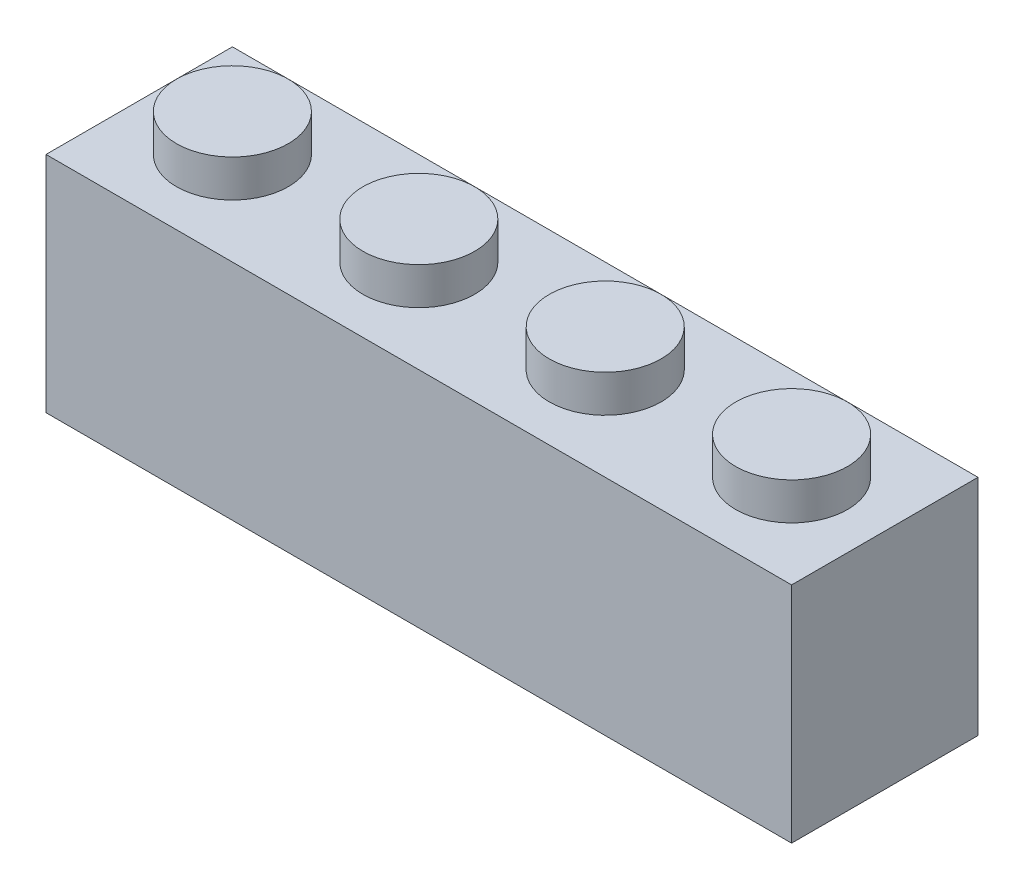
SolidWorks part; units mm, degrees
ref_plane "Front Plane" through (0, 0, 0) normal (0, 0, 1) x (1, 0, 0)
ref_plane "Top Plane" through (0, 0, 0) normal (0, 1, 0) x (1, 0, 0)
ref_plane "Right Plane" through (0, 0, 0) normal (1, 0, 0) x (0, 0, -1)
sketch "Sketch1" plane through (0, 0, 0) normal (0, 1, 0) x (1, 0, 0)
  line L0 (-7.5, 0) -> (-2.5, 0)
  line L1 (-10, -2.5) -> (10, -2.5)
  line L2 (-10, -2.5) -> (-10, 2.5)
  line L3 (-10, 2.5) -> (10, 2.5)
  line L4 (10, -2.5) -> (10, 2.5)
  line L5 (-10, -2.5) -> (10, 2.5) construction
  line L6 (-10, 2.5) -> (10, -2.5) construction
  line L7 (-9, -1.5) -> (9, -1.5)
  line L8 (-9, -1.5) -> (-9, 1.5)
  line L9 (-9, 1.5) -> (9, 1.5)
  line L10 (9, -1.5) -> (9, 1.5)
  line L11 (-9, -1.5) -> (9, 1.5) construction
  line L12 (-9, 1.5) -> (9, -1.5) construction
  circle A0 centre (-7.5, 0) radius 1.5
  circle A1 centre (-7.5, 0) radius 0.75
  circle A2 centre (-2.5, 0) radius 0.75
  circle A3 centre (-2.5, 0) radius 1.5
  circle A4 centre (2.5, 0) radius 0.75
  circle A5 centre (2.5, 0) radius 1.5
  circle A6 centre (7.5, 0) radius 0.75
  circle A7 centre (7.5, 0) radius 1.5
  circle A8 centre (-5, 0) radius 1
  circle A9 centre (0, 0) radius 1
  circle A10 centre (5, 0) radius 1
  point P0 (0, 0)
  point P9 (0, 0)
  dimension "D4" = 3
  dimension "D6" = 1.5
  dimension "D1" = 5
  dimension "D2" = 20
  dimension "D3" = 2.5
  dimension "D5" = 2.5
  dimension "D7" = 1
  dimension "D8" = 1
  dimension "D9" = 4
  dimension "D10" = 3
extrude "Boss-Extrude1" add sketch "Sketch1" along normal blind 2 contours A1 A0 | A1 | A2 | A3 A2 | A4 | A5 A4 | A7 A6 | A6 region at (-6.4693, 0, 1.0307) region at (-8.2288, 0, 0) region at (-2.5, 0, -0.7288) region at (-3.5307, 0, -1.0307) region at (3.5307, 0, -1.0307) region at (8.5307, 0, -1.0307) region at (2.5, 0, 0) region at (7.5, 0, 0)
extrude "Boss-Extrude2" add sketch "Sketch1<3>" along normal blind 1 contours L2 L3 L4 L1
sketch "Sketch1<3>" plane through (0, 0, 0) normal (0, 1, 0) x (1, 0, 0) same geometry as "Sketch1"
extrude "Cut-Extrude1" cut sketch "Sketch1<4>" along normal blind 1 contours A1 | A2 | A4 | A6 region at (-8.2288, 0, 0) region at (-2.5, 0, -0.7288) region at (2.5, 0, 0) region at (7.5, 0, 0)
sketch "Sketch1<4>" plane through (0, 0, 0) normal (0, 1, 0) x (1, 0, 0) same geometry as "Sketch1"
extrude "Boss-Extrude4" add sketch "Sketch1<6>" against normal blind 5 contours L1 L4 L3 L2 L10 L7 L8 L9 | L0 A8 | L0 A8 | A9 | A10 region at (-5, 0, -0.4244) region at (-5, 0, 0.4244) region at (0, 0, 0) region at (5, 0, 0) region at (-9.7938, 0, 0)
sketch "Sketch1<6>" plane through (0, 0, 0) normal (0, 1, 0) x (1, 0, 0) same geometry as "Sketch1"
